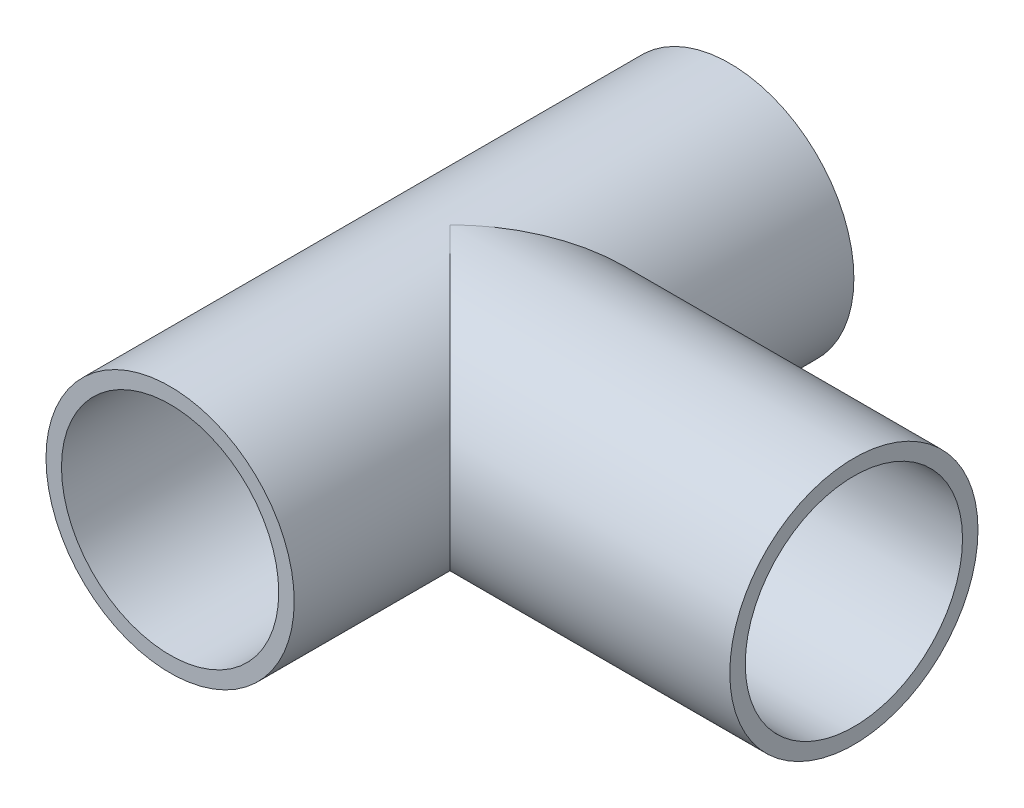
SolidWorks part; units mm, degrees
material "PE High Density"
ref_plane "Front Plane" through (0, 0, 0) normal (0, 0, 1) x (1, 0, 0)
ref_plane "Top Plane" through (0, 0, 0) normal (0, 1, 0) x (1, 0, 0)
ref_plane "Right Plane" through (0, 0, 0) normal (1, 0, 0) x (0, 0, -1)
other "Center of Mass"
sketch "Through Section" plane through (0, 0, 0) normal (0, 0, 1) x (1, 0, 0)
  circle A0 centre (0, 0) radius 161.925
  circle A1 centre (0, 0) radius 141.732
  dimension "D1" = 283.464
  dimension "D2" = 323.85
extrude "Through Section Extrude" add sketch "Through Section" along normal mid plane 730.25
ref_plane "E Plane" through (527.05, 0, 0) normal (1, 0, 0) x (0, 0, -1)
sketch "Orthogonal Section OD" plane through (527.05, 0, 0) normal (1, 0, 0) x (0, 0, -1)
  circle A0 centre (0, 0) radius 161.925
  dimension "D3" = 323.85
extrude "Orthogonal Section OD Extrude" add sketch "Orthogonal Section OD" against normal up to surface (365.125 mm away) up to face at (161.925, 0, 365.125)
sketch "Orthogonal Section ID" plane through (527.05, 0, 0) normal (1, 0, 0) x (0, 0, -1)
  circle A0 centre (0, 0) radius 141.732
  circle A1 centre (0, 0) radius 161.925 construction
  dimension "D1" = 283.464
extrude "Orthogonal Section ID Cut" cut sketch "Orthogonal Section ID" against normal up to surface (527.05 mm away) up to plane "Right Plane"
other "Center of Mass Reference Point1"
equation "\"ID\"= 11.160in'EPG"
equation "\"OD\"= 12.75in'EPG"
equation "\"A\"= 8in'EPG"
equation "\"C\"= 28.75in'EPG"
equation "\"E\"= 8in'EPG"
equation "\"D1@Through Section\" = \"ID\""
equation "\"D2@Through Section\" = \"OD\""
equation "\"D1@Through Section Extrude\" = \"C\""
equation "\"D3@Orthogonal Section OD\" = \"OD\""
equation "\"D1@Orthogonal Section ID\" = \"ID\""
